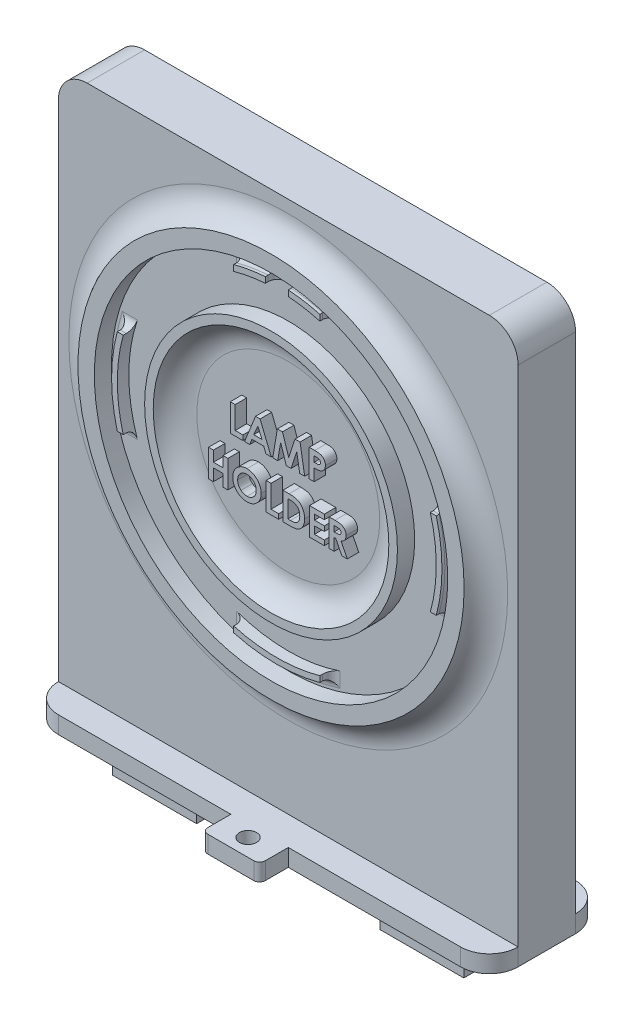
SolidWorks part; units mm, degrees
ref_plane "Front Plane" through (0, 0, 0) normal (0, 0, 1) x (1, 0, 0)
ref_plane "Top Plane" through (0, 0, 0) normal (0, 1, 0) x (1, 0, 0)
ref_plane "Right Plane" through (0, 0, 0) normal (1, 0, 0) x (0, 0, -1)
sketch "Sketch1" plane through (0, 0, 0) normal (0, 0, 1) x (1, 0, 0)
  line L1 (-40, 55.35) -> (40, 55.35)
  line L2 (-40, 55.35) -> (-40, -55.35)
  line L3 (-40, -55.35) -> (40, -55.35)
  line L4 (40, 55.35) -> (40, -55.35)
  line L5 (-40, 55.35) -> (40, -55.35) construction
  line L6 (-40, -55.35) -> (40, 55.35) construction
  point P0 (0, 0)
  dimension "D1" = 80
  dimension "D2" = 110.7
extrude "Boss-Extrude1" add sketch "Sketch1" along normal blind 10
sketch "Sketch3" plane through (0, 0, 0) normal (0, 0, -1) x (-1, 0, 0)
  line L0 (0, -55.35) -> (0, -45) construction
  line L1 (40, -55.35) -> (-40, -55.35) construction
  line L2 (-40, 55.35) -> (40, 55.35) construction
  line L8 (20.95, -57.2) -> (25.55, -57.2) construction
  line L9 (-20.95, -59.05) -> (-15.95, -59.05)
  line L10 (-30.55, -59.05) -> (-25.55, -59.05)
  line L11 (-30.55, -59.05) -> (-30.55, -61.75)
  line L12 (-30.55, -61.75) -> (-15.95, -61.75)
  line L13 (-15.95, -59.05) -> (-15.95, -61.75)
  line L14 (-30.55, -59.05) -> (-15.95, -61.75) construction
  line L15 (-30.55, -61.75) -> (-15.95, -59.05) construction
  line L16 (-25.55, -55.35) -> (-20.95, -55.35)
  line L17 (-25.55, -55.35) -> (-25.55, -59.05)
  line L19 (-20.95, -55.35) -> (-20.95, -59.05)
  line L20 (-25.55, -55.35) -> (-20.95, -59.05) construction
  line L21 (-25.55, -59.05) -> (-20.95, -55.35) construction
  line L22 (30.55, -59.05) -> (30.55, -61.75)
  line L23 (30.55, -61.75) -> (15.95, -61.75)
  line L24 (15.95, -59.05) -> (15.95, -61.75)
  line L25 (20.95, -59.05) -> (15.95, -59.05)
  line L26 (20.95, -55.35) -> (20.95, -59.05)
  line L27 (25.55, -55.35) -> (20.95, -55.35)
  line L28 (25.55, -55.35) -> (25.55, -59.05)
  line L29 (30.55, -59.05) -> (25.55, -59.05)
  point P5 (0, -50.175)
  point P12 (-23.25, -60.4)
  point P17 (-23.25, -57.2)
  dimension "D1" = 110.7
  dimension "D2" = 16.75
  dimension "D3" = 2.7
  dimension "D4" = 14.6
  dimension "D5" = 4.6
  dimension "D6" = 3.7
extrude "Boss-Extrude2" add sketch "Sketch3" against normal blind 10
sketch "Sketch11" plane through (0, 0, 10) normal (0, 0, 1) x (1, 0, 0)
  line L19 (40, -55.35) -> (40, 55.35) construction
  line L28 (-40, 55.35) -> (40, 55.35)
  line L29 (-40, 55.35) -> (-40, 40.35)
  line L30 (-40, 40.35) -> (40, 40.35)
  line L31 (40, 55.35) -> (40, 40.35)
  dimension "D1" = 15
extrude "Cut-Extrude1" cut sketch "Sketch11" against normal blind 10 contours L29 L28 L31 L30
sketch "Sketch4" plane through (0, -55.35, 0) normal (0, -1, 0) x (1, 0, 0)
  line L0 (0, 10) -> (0, 0) construction
  line L1 (-20.95, 10) -> (20.95, 10) construction
  line L2 (5, -5) -> (35, -5)
  line L3 (-40, 10) -> (40, 10)
  line L4 (-40, 10) -> (-40, 0)
  line L5 (-40, 0) -> (40, 0)
  line L6 (40, 10) -> (40, 0)
  line L7 (-40, 10) -> (40, 0) construction
  line L8 (-40, 0) -> (40, 10) construction
  line L9 (-35, 15) -> (-5, 15)
  line L10 (-40, 10) -> (-40, 0)
  line L11 (-35, -5) -> (-5, -5)
  line L12 (40, 10) -> (40, 0)
  line L13 (-40, 15) -> (40, -5) construction
  line L14 (-40, -5) -> (40, 15) construction
  line L16 (-5, -5) -> (-5, -9)
  line L17 (-4, -10) -> (4, -10)
  line L18 (5, -5) -> (5, -9)
  line L20 (-40, 5) -> (40, 5) construction
  line L21 (-5, 15) -> (-5, 19)
  line L22 (5, 15) -> (5, 19)
  line L23 (-4, 20) -> (4, 20)
  line L24 (5, 15) -> (35, 15)
  arc A0 (35, 15) -> (40, 10) centre (35, 10) cw
  arc A1 (35, -5) -> (40, 0) centre (35, 0) ccw
  arc A2 (-40, 0) -> (-35, -5) centre (-35, 0) ccw
  arc A3 (-35, 15) -> (-40, 10) centre (-35, 10) ccw
  circle A4 centre (0, -7) radius 1.5
  arc A5 (-5, -9) -> (-4, -10) centre (-4, -9) ccw
  arc A6 (4, -10) -> (5, -9) centre (4, -9) ccw
  circle A7 centre (0, 17) radius 1.5
  arc A8 (-5, 19) -> (-4, 20) centre (-4, 19) cw
  arc A9 (4, 20) -> (5, 19) centre (4, 19) cw
  point P5 (0, 5)
  point P11 (0, 5)
  point P37 (-5, -10)
  line M5 (20.95, 10) -> (-20.95, 10)
  line M7 (-20.95, 0) -> (20.95, 0)
  dimension "D3" = 5
  dimension "D6" = 3
  dimension "D7" = 1
  dimension "D1" = 20
  dimension "D2" = 80
  dimension "D4" = 5
  dimension "D5" = 10
  dimension "D8" = 3
extrude "Boss-Extrude3" add sketch "Sketch4" against normal blind 3 contours A9 L23 A8 L21 L9 A3 L3 A0 L24 L22 A7 M5 | L17 A6 L18 L2 A1 L5 A2 L11 L16 A5 A4 M7 region at (0, -55.35, -2.9637) region at (0, -55.35, 12.9637)
sketch "Sketch5" plane through (0, 0, 10) normal (0, 0, 1) x (1, 0, 0)
  circle A0 centre (0, 0) radius 33.6
  circle A1 centre (0, 0) radius 30.75
  dimension "D1" = 61.5
  dimension "D2" = 67.2
extrude "Boss-Extrude4" add sketch "Sketch5" along normal blind 3
sketch "Sketch12" plane through (0, 0, 10) normal (0, 0, 1) x (1, 0, 0)
  line L0 (0, 28.75) -> (0, 27.75) construction
  line L1 (-7.5, 29) -> (7.5, 29)
  line L2 (-7.5, 29) -> (-7.5, -29)
  line L3 (-7.5, -29) -> (7.5, -29)
  line L4 (7.5, 29) -> (7.5, -29)
  line L5 (-7.5, 29) -> (7.5, -29) construction
  line L6 (-7.5, -29) -> (7.5, 29) construction
  line L7 (-29, 7.5) -> (29, 7.5)
  line L8 (-29, 7.5) -> (-29, -7.5)
  line L9 (-29, -7.5) -> (29, -7.5)
  line L10 (29, 7.5) -> (29, -7.5)
  line L11 (-29, 7.5) -> (29, -7.5) construction
  line L12 (-29, -7.5) -> (29, 7.5) construction
  line L14 (-2, 28.8222) -> (2, 28.8222)
  line L15 (-2, 28.8222) -> (-2, 27.6778)
  line L16 (-2, 27.6778) -> (2, 27.6778)
  line L17 (2, 28.8222) -> (2, 27.6778)
  line L18 (-2, 28.8222) -> (2, 27.6778) construction
  line L19 (-2, 27.6778) -> (2, 28.8222) construction
  circle A0 centre (0, 0) radius 27.75
  circle A1 centre (0, 0) radius 28.75
  point P14 (0, 28.25)
  dimension "D1" = 55.5
  dimension "D2" = 57.5
  dimension "D3" = 15
  dimension "D4" = 58
  dimension "D5" = 15
  dimension "D6" = 58
  dimension "D7" = 4
extrude "Boss-Extrude5" add sketch "Sketch12" along normal blind 2 contours L15 A1 L2 A0 | L4 A1 L17 A0 | L7 A1 L9 A0 | L9 A1 L7 A0 | L2 A1 L4 A0 region at (-4.7656, 27.7983, 10) region at (4.7656, 27.7983, 10) region at (-27.9111, 0, 10) region at (27.9111, 0, 10) region at (0, -27.9111, 10)
sketch "Sketch13" plane through (0, 0, 10) normal (0, 0, 1) x (1, 0, 0)
  circle A0 centre (0, 0) radius 22
  circle A1 centre (0, 0) radius 20.5
  dimension "D1" = 41
  dimension "D2" = 44
extrude "Boss-Extrude6" add sketch "Sketch13" along normal blind 3
fillet "Fillet1" radius 5 2 edges at (20.5, 0, 10) (33.6, 0, 10)
fillet "Fillet2" radius 1.5 15 edges at (27.2359, -7.5, 10) (28.75, 0, 10) (27.2359, 7.5, 10) (7.5, 27.2359, 10) (4.7725, 28.3511, 10) (2, 28.1791, 10) (-2, 28.1791, 10) (-4.7725, 28.3511, 10) (-7.5, 27.2359, 10) (-27.2359, 7.5, 10) (-28.75, 0, 10) (-27.2359, -7.5, 10) (7.5, -27.2359, 10) (0, -28.75, 10) (-7.5, -27.2359, 10)
fillet "Fillet3" radius 5 2 edges at (40, 40.35, 5) (-40, 40.35, 5)
sketch "Sketch14" plane through (0, 0, 10) normal (0, 0, 1) x (1, 0, 0)
  line L0 (15.7884, 2.0222) -> (-15.7884, 2.0222) construction
  circle A2 centre (0, 0) radius 15.9174 construction
  text T0 "<b>LAMP</b>\r\n<b>HOLDER</b>" font "Century Gothic" height in points 18
  point P9 (0, 0)
  point P11 (0, 0)
extrude "Boss-Extrude7" add sketch "Sketch14" along normal blind 2
